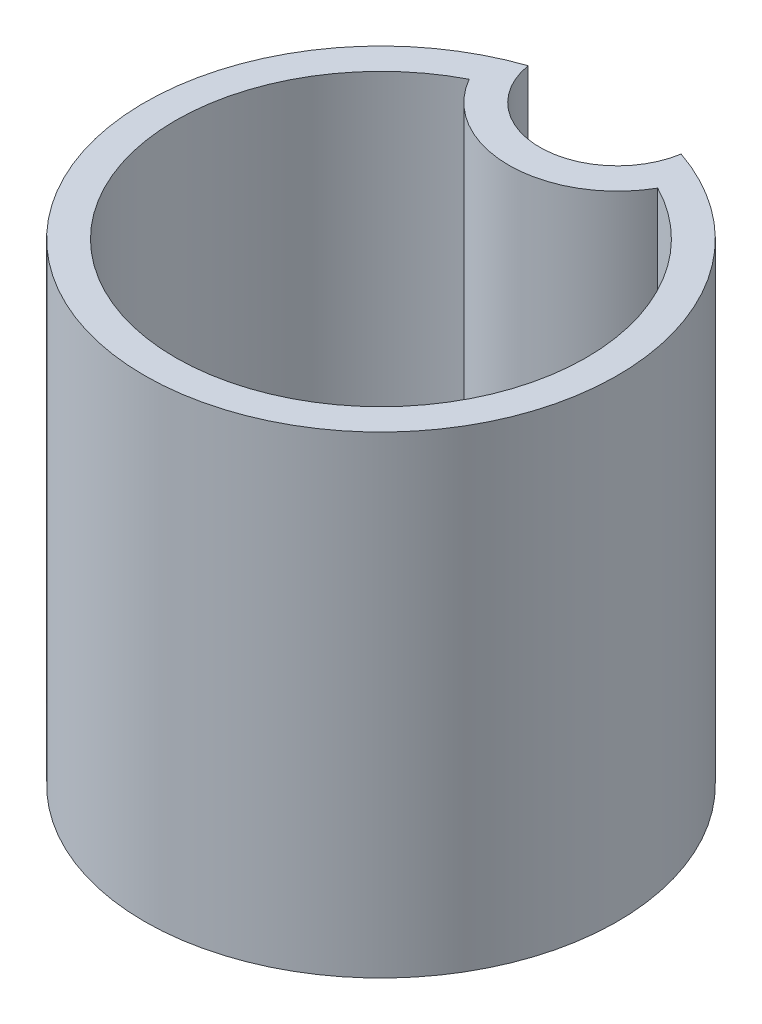
SolidWorks part; units mm, degrees
material "ABS"
ref_plane "Front Plane" through (0, 0, 0) normal (0, 0, 1) x (1, 0, 0)
ref_plane "Top Plane" through (0, 0, 0) normal (0, 1, 0) x (1, 0, 0)
ref_plane "Right Plane" through (0, 0, 0) normal (1, 0, 0) x (0, 0, -1)
sketch "Sketch1" plane through (0, 0, 0) normal (0, 1, 0) x (1, 0, 0)
  circle A0 centre (0, 0) radius 38.1
  circle A1 centre (0, 0) radius 33.1
  circle A2 centre (0, 38.1) radius 12.5
  circle A3 centre (0, 38.1) radius 17.5
  dimension "D1" = 76.2
  dimension "D2" = 5
  dimension "D3" = 25
  dimension "D4" = 5
extrude "Boss-Extrude1" add sketch "Sketch1" along normal blind 76.2 contours A3 A1 A0 | A0 A3 A1 A2 | A1 A3 A2 | A1 A3 A0 A2 region at (-19.4816, 0, 31.5151) region at (13.9313, 0, -32.733) region at (-13.9313, 0, -32.733) region at (0, 0, -25.5165)
extrude "Boss-Extrude2" add sketch "Sketch1<3>" along normal blind 5 contours A3 A1 region at (0, 0, 2.2776)
sketch "Sketch1<3>" plane through (0, 0, 0) normal (0, 1, 0) x (1, 0, 0) same geometry as "Sketch1"
